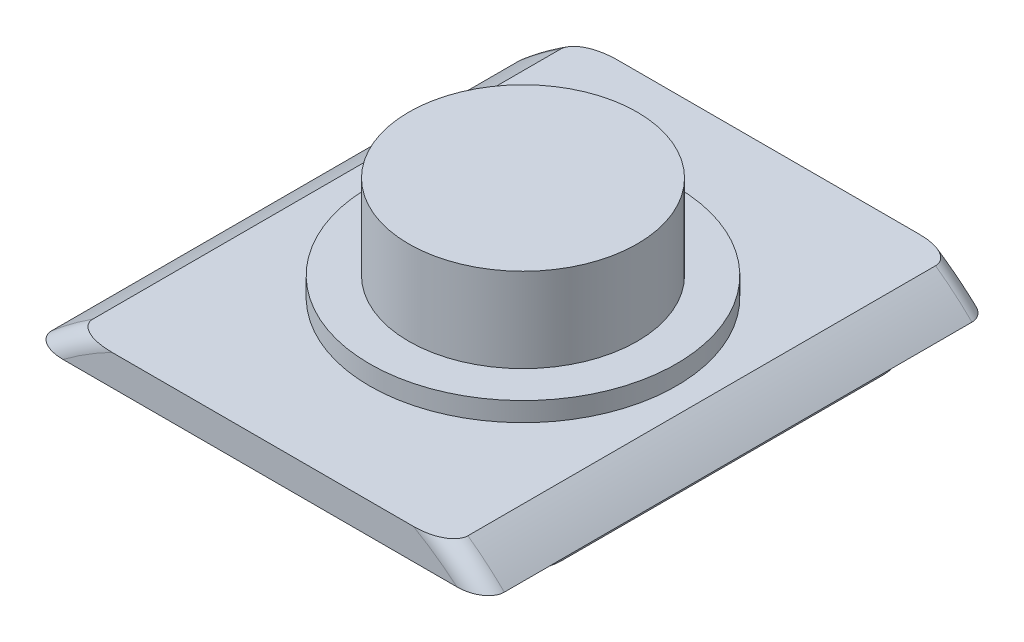
SolidWorks part; units mm, degrees
ref_plane "Front Plane" through (0, 0, 0) normal (0, 0, 1) x (1, 0, 0)
ref_plane "Top Plane" through (0, 0, 0) normal (0, 1, 0) x (1, 0, 0)
ref_plane "Right Plane" through (0, 0, 0) normal (1, 0, 0) x (0, 0, -1)
sketch "Sketch3" plane through (0, 0, 0) normal (0, 0, 1) x (1, 0, 0)
  circle A0 centre (0, 0) radius 40
  dimension "D1" = 80
extrude "Boss-Extrude2" add sketch "Sketch3" along normal blind 66
sketch "Sketch4" plane through (0, 0, 66) normal (0, 0, 1) x (1, 0, 0)
  line L0 (0, 0) -> (0, 40)
  line L1 (0, 0) -> (-43.4667, 11.6469)
  circle A0 centre (0, 0) radius 40 construction
  arc A1 (0, 40) -> (-43.4667, 11.6469) centre (0, -7.4948) ccw
  dimension "D1" = 45
  dimension "D2" = 75
extrude "Boss-Extrude3" add sketch "Sketch4" against normal blind 66
fillet "Fillet1" radius 1 1 edges at (-43.4667, 11.6469, 33)
fillet "Fillet2" radius 2.5 8 edges at (24.3505, -31.7341, 0) (-40.4815, 10.847, 0) (-42.9742, 11.8862, 0) (24.3505, -31.7341, 66) (-40.4815, 10.847, 66) (-42.9742, 11.8862, 66) (-25.4464, 32.608, 0) (-25.4464, 32.608, 66)
ref_plane "Plane1" through (0, 28.5, 0) normal (0, 1, 0) x (1, 0, 0)
sketch "Sketch5" plane through (0, 28.5, 0) normal (0, 1, 0) x (1, 0, 0)
  line L4 (0, -2.5) -> (0, -63.5) construction
  line L5 (-50, 17) -> (50, 17)
  line L6 (-50, 17) -> (-50, -83)
  line L7 (-50, -83) -> (50, -83)
  line L16 (50, 17) -> (50, -83)
  line L17 (-50, 17) -> (50, -83) construction
  line L18 (-50, -83) -> (50, 17) construction
  point P0 (0, -33)
  dimension "D1" = 100
  dimension "D2" = 100
extrude "Cut-Extrude1" cut sketch "Sketch5" against normal through all
sketch "Sketch6" plane through (0, 28.5, 0) normal (0, -1, 0) x (1, 0, 0)
  line L1 (-21, 59) -> (21, 59)
  line L2 (-26, 54) -> (-26, 12)
  line L3 (-21, 7) -> (21, 7)
  line L4 (26, 54) -> (26, 12)
  line L5 (-26, 59) -> (26, 7) construction
  line L6 (-26, 7) -> (26, 59) construction
  line L8 (-30.986, 63.5) -> (-30.986, 2.5) construction
  arc A0 (-26, 12) -> (-21, 7) centre (-21, 12) ccw
  arc A1 (21, 7) -> (26, 12) centre (21, 12) ccw
  arc A2 (21, 59) -> (26, 54) centre (21, 54) cw
  arc A3 (-21, 59) -> (-26, 54) centre (-21, 54) ccw
  point P0 (0, 33)
  point P10 (-30.986, 33)
  dimension "D3" = 5
  dimension "D1" = 52
  dimension "D2" = 52
extrude "Boss-Extrude4" add sketch "Sketch6" along normal blind 2.25
ref_plane "Plane2" through (0, 32.5, 0) normal (0, 1, 0) x (1, 0, 0)
sketch "Sketch7" plane through (0, 32.5, 0) normal (0, 1, 0) x (1, 0, 0)
  line L0 (0, -2.5) -> (0, -63.5) construction
  line L1 (-50, 17) -> (50, 17)
  line L2 (-50, 17) -> (-50, -83)
  line L3 (-50, -83) -> (50, -83)
  line L4 (50, 17) -> (50, -83)
  line L5 (-50, 17) -> (50, -83) construction
  line L6 (-50, -83) -> (50, 17) construction
  point P0 (0, -33)
  dimension "D1" = 100
  dimension "D2" = 100
extrude "Cut-Extrude2" cut sketch "Sketch7" along normal through all
sketch "Sketch8" plane through (0, 32.5, 0) normal (0, 1, 0) x (1, 0, 0)
  line L0 (-25.6158, -63.5) -> (-25.6158, -2.5) construction
  circle A0 centre (0, -33) radius 20
  point P7 (-25.6158, -33)
  dimension "D1" = 40
extrude "Boss-Extrude5" add sketch "Sketch8" along normal blind 2.5 contours A0
sketch "Sketch9" plane through (0, 35, 0) normal (0, 1, 0) x (1, 0, 0)
  circle A0 centre (0, -33) radius 14.9
  dimension "D1" = 29.8
extrude "Boss-Extrude6" add sketch "Sketch9" along normal blind 11
